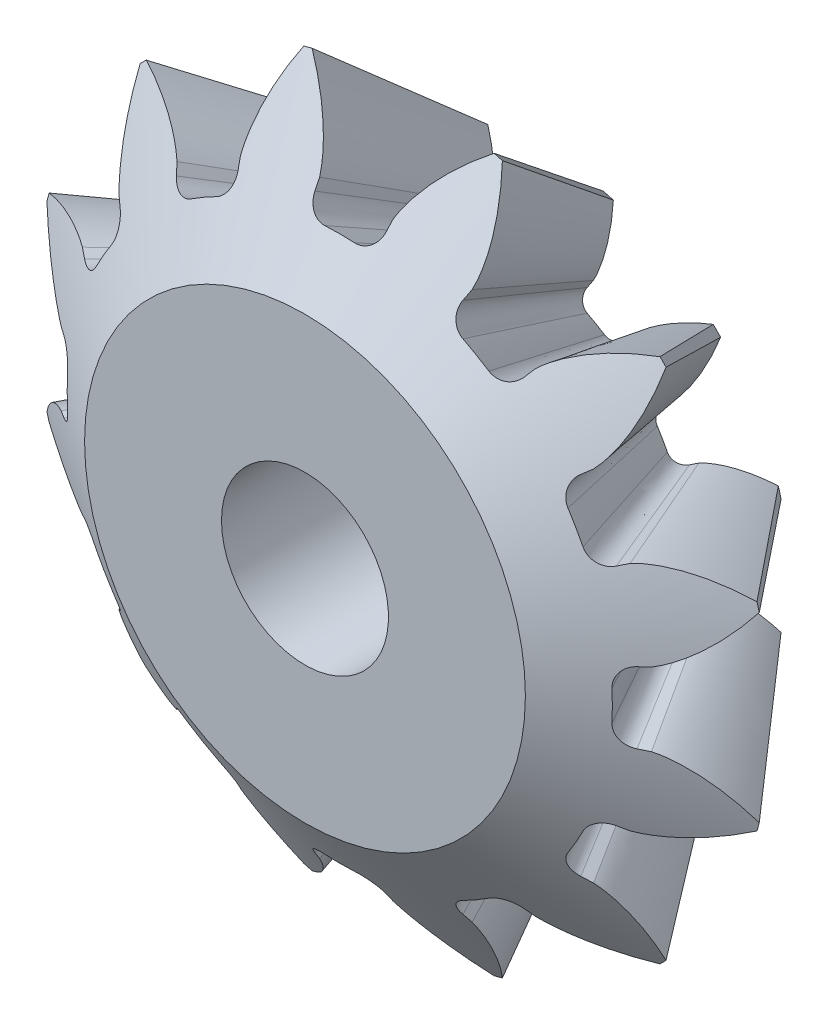
SolidWorks part; units mm, degrees
ref_plane "Front Plane" through (0, 0, 0) normal (0, 0, 1) x (1, 0, 0)
ref_plane "Top Plane" through (0, 0, 0) normal (0, 1, 0) x (1, 0, 0)
ref_plane "Right Plane" through (0, 0, 0) normal (1, 0, 0) x (0, 0, -1)
ref_axis "Gear Axis" through (0, 0, -1.3521) along (0, 0, 1)
sketch "Blank Sketch" plane through (0, 0, 0) normal (0, 1, 0) x (1, 0, 0)
  line L0 (0, 0) -> (0, -27.0416) construction
  line L1 (0, 0) -> (15, -22.5) construction
  line L2 (0, 0) -> (10.0077, -15.0115) construction
  line L3 (6.2136, -17.5409) -> (11.62, -13.9367)
  line L4 (11.62, -13.9367) -> (17.6117, -20.7589)
  line L5 (17.6117, -20.7589) -> (10.5604, -25.4597)
  line L6 (10.5604, -25.4597) -> (4, -25.4597)
  line L7 (4, -25.4597) -> (4, -17.5409)
  line L8 (4, -17.5409) -> (6.2136, -17.5409)
  line L9 (15, -22.5) -> (17.6117, -20.7589) construction
  line L10 (15, -22.5) -> (10.5604, -25.4597) construction
  line L11 (10.0077, -15.0115) -> (6.2136, -17.5409) construction
  dimension "Axis" = 27.0416
  dimension "Cone" = 33.69
  dimension "Heel" = 27.0416
  dimension "Toe Cone" = 33.69
  dimension "Toe" = 18.0416
  dimension "Heel Square" = 90
  dimension "Addendum" = 3.1389
  dimension "Root Square" = 90
  dimension "Heel Rim" = 5.3357
  dimension "Toe Square" = 90
  dimension "Toe Rim" = 4.5599
  dimension "Front Square" = 90
  dimension "Face" = 7.602
  dimension "Back" = 6.5604
  dimension "Front" = 2.2136
revolve "Blank" add sketch "Blank Sketch" angle 360 about L0
sketch "Cone Sketch" plane through (0, 0, 0) normal (0, 1, 0) x (1, 0, 0)
  line L0 (0, 0) -> (0, -27.0416) construction
  line L1 (0, 0) -> (16.3868, -24.5801)
  line L2 (0, 0) -> (8.6209, -12.9314)
  dimension "Axis" = 27.0416
  dimension "Toe Cone" = 33.69
  dimension "Heel Cone" = 33.69
  dimension "Heel" = 29.5416
  dimension "Toe" = 15.5416
ref_plane "Heel Plane" through (16.3868, 0, 24.5801) normal (0.5547, 0, 0.8321) x (0.8321, 0, -0.5547)
ref_plane "Toe Plane" through (8.6209, 0, 12.9314) normal (0.5547, 0, 0.8321) x (0.8321, 0, -0.5547)
sketch "Heel Section Sketch" plane through (16.3868, 0, 24.5801) normal (0.5547, 0, 0.8321) x (0.8321, 0, -0.5547)
  line L0 (0, 0) -> (-19.6944, 0) construction
  line L1 (-1.0889, 1.9222) -> (-1.6346, 1.8659)
  line L2 (-1.0889, -1.9222) -> (-1.6346, -1.8659)
  line L3 (4.9712, 7.7503) -> (4.9712, -7.7503)
  arc A0 (-1.6346, 1.8659) -> (-2.5646, 0.786) centre (-1.5279, 0.8335) ccw
  arc A1 (-2.5646, -0.786) -> (-1.6346, -1.8659) centre (-1.5279, -0.8335) ccw
  arc A2 (-2.5646, -0.786) -> (-2.5646, 0.786) centre (-19.6944, 0) ccw
  spline S0 degree 4 poles (-1.2507, 1.887) (-1.2032, 1.896) (-1.1208, 1.9133) (-1.0358, 1.9352) (-0.8462, 1.9918) (-0.6823, 2.0516) (-0.464, 2.1381) (-0.2472, 2.238) (-0.0046, 2.3596) (0.2268, 2.4884) (0.4574, 2.6259) (0.6814, 2.7703) (0.921, 2.9344) (1.2087, 3.1455) (1.5406, 3.4086) (1.9115, 3.7305) (2.2985, 4.0977) (2.6707, 4.4833) (3.0253, 4.8797) (3.3677, 5.2955) (3.6895, 5.7131) (4.0058, 6.1591) (4.2547, 6.5304) (4.4822, 6.8974) (4.6632, 7.1957) (4.8973, 7.6113) (5.0277, 7.8523) (5.2374, 8.2598) (5.307, 8.4069) (5.363, 8.5216) knots 0 0 0 0 0 0.016753 0.031571 0.050064 0.068907 0.096646 0.124386 0.152126 0.179865 0.207605 0.235344 0.263084 0.300343 0.355823 0.411302 0.466781 0.52226 0.577739 0.633218 0.688697 0.744176 0.799656 0.827395 0.855135 0.910614 0.955307 1 1 1 1 1 construction
  spline S1 degree 4 poles (-1.0889, 1.9222) (-1.058, 1.9301) (-0.9897, 1.9489) (-0.8462, 1.9918) (-0.6823, 2.0516) (-0.464, 2.1381) (-0.2472, 2.238) (-0.0046, 2.3596) (0.2268, 2.4884) (0.4574, 2.6259) (0.6814, 2.7703) (0.921, 2.9344) (1.2087, 3.1455) (1.5406, 3.4086) (1.9115, 3.7305) (2.2985, 4.0977) (2.6707, 4.4833) (3.0253, 4.8797) (3.3677, 5.2955) (3.6895, 5.7131) (4.0058, 6.1591) (4.2547, 6.5304) (4.4822, 6.8974) (4.6632, 7.1957) (4.83, 7.4919) (4.9147, 7.6452) (4.9712, 7.7503) knots 0.016753 0.016753 0.016753 0.016753 0.016753 0.031571 0.050064 0.068907 0.096646 0.124386 0.152126 0.179865 0.207605 0.235344 0.263084 0.300343 0.355823 0.411302 0.466781 0.52226 0.577739 0.633218 0.688697 0.744176 0.799656 0.827395 0.855135 0.910614 0.910614 0.910614 0.910614 0.910614
  spline S2 degree 4 poles (-1.2507, -1.887) (-1.2032, -1.896) (-1.1208, -1.9133) (-1.0358, -1.9352) (-0.8462, -1.9918) (-0.6823, -2.0516) (-0.464, -2.1381) (-0.2472, -2.238) (-0.0046, -2.3596) (0.2268, -2.4884) (0.4574, -2.6259) (0.6814, -2.7703) (0.921, -2.9344) (1.2087, -3.1455) (1.5406, -3.4086) (1.9115, -3.7305) (2.2985, -4.0977) (2.6707, -4.4833) (3.0253, -4.8797) (3.3677, -5.2955) (3.6895, -5.7131) (4.0058, -6.1591) (4.2547, -6.5304) (4.4822, -6.8974) (4.6632, -7.1957) (4.8973, -7.6113) (5.0277, -7.8523) (5.2374, -8.2598) (5.307, -8.4069) (5.363, -8.5216) knots 0 0 0 0 0 0.016753 0.031571 0.050064 0.068907 0.096646 0.124386 0.152126 0.179865 0.207605 0.235344 0.263084 0.300343 0.355823 0.411302 0.466781 0.52226 0.577739 0.633218 0.688697 0.744176 0.799656 0.827395 0.855135 0.910614 0.955307 1 1 1 1 1 construction
  spline S3 degree 4 poles (-1.0889, -1.9222) (-1.058, -1.9301) (-0.9897, -1.9489) (-0.8462, -1.9918) (-0.6823, -2.0516) (-0.464, -2.1381) (-0.2472, -2.238) (-0.0046, -2.3596) (0.2268, -2.4884) (0.4574, -2.6259) (0.6814, -2.7703) (0.921, -2.9344) (1.2087, -3.1455) (1.5406, -3.4086) (1.9115, -3.7305) (2.2985, -4.0977) (2.6707, -4.4833) (3.0253, -4.8797) (3.3677, -5.2955) (3.6895, -5.7131) (4.0058, -6.1591) (4.2547, -6.5304) (4.4822, -6.8974) (4.6632, -7.1957) (4.83, -7.4919) (4.9147, -7.6452) (4.9712, -7.7503) knots 0.016753 0.016753 0.016753 0.016753 0.016753 0.031571 0.050064 0.068907 0.096646 0.124386 0.152126 0.179865 0.207605 0.235344 0.263084 0.300343 0.355823 0.411302 0.466781 0.52226 0.577739 0.633218 0.688697 0.744176 0.799656 0.827395 0.855135 0.910614 0.910614 0.910614 0.910614 0.910614
  dimension "Root" = 17.1478
  dimension "Fillet" = 1.0378
  dimension "Centre" = 19.6944
sketch "Toe Section Sketch" plane through (8.6209, 0, 12.9314) normal (0.5547, 0, 0.8321) x (0.8321, 0, -0.5547)
  line L0 (0, 0) -> (-10.3611, 0) construction
  line L1 (-0.5729, 1.0113) -> (-0.8599, 0.9816)
  line L2 (-0.5729, -1.0113) -> (-0.8599, -0.9816)
  line L3 (2.6153, 4.0774) -> (2.6153, -4.0774)
  arc A0 (-0.8599, 0.9816) -> (-1.3492, 0.4135) centre (-0.8038, 0.4385) ccw
  arc A1 (-1.3492, -0.4135) -> (-0.8599, -0.9816) centre (-0.8038, -0.4385) ccw
  arc A2 (-1.3492, -0.4135) -> (-1.3492, 0.4135) centre (-10.3611, 0) ccw
  spline S0 degree 4 poles (-0.658, 0.9927) (-0.633, 0.9975) (-0.5896, 1.0066) (-0.5449, 1.0181) (-0.4452, 1.0479) (-0.3589, 1.0793) (-0.2441, 1.1248) (-0.13, 1.1774) (-0.0024, 1.2414) (0.1193, 1.3091) (0.2407, 1.3815) (0.3584, 1.4574) (0.4846, 1.5439) (0.6358, 1.6546) (0.8107, 1.7936) (1.0052, 1.9619) (1.2098, 2.1568) (1.4042, 2.357) (1.593, 2.5698) (1.7694, 2.7815) (1.9449, 3.0128) (2.1009, 3.2281) (2.2685, 3.4846) (2.3965, 3.6866) (2.5615, 3.9767) (2.6479, 4.1363) (2.7514, 4.3381) (2.7948, 4.4281) (2.8204, 4.4812) knots 0 0 0 0 0 0.016753 0.031571 0.050064 0.068907 0.096646 0.124386 0.152126 0.179865 0.207605 0.235344 0.263084 0.300343 0.355823 0.411302 0.466781 0.52226 0.577739 0.633218 0.688697 0.744176 0.799656 0.855135 0.910614 0.955307 1 1 1 1 1 construction
  spline S1 degree 4 poles (-0.5729, 1.0113) (-0.5566, 1.0154) (-0.5207, 1.0253) (-0.4452, 1.0479) (-0.3589, 1.0793) (-0.2441, 1.1248) (-0.13, 1.1774) (-0.0024, 1.2414) (0.1193, 1.3091) (0.2407, 1.3815) (0.3584, 1.4574) (0.4846, 1.5439) (0.6358, 1.6546) (0.8107, 1.7936) (1.0052, 1.9619) (1.2098, 2.1568) (1.4042, 2.357) (1.593, 2.5698) (1.7694, 2.7815) (1.9449, 3.0128) (2.1009, 3.2281) (2.2685, 3.4846) (2.3965, 3.6866) (2.5266, 3.9153) (2.5856, 4.0221) (2.6153, 4.0774) knots 0.016753 0.016753 0.016753 0.016753 0.016753 0.031571 0.050064 0.068907 0.096646 0.124386 0.152126 0.179865 0.207605 0.235344 0.263084 0.300343 0.355823 0.411302 0.466781 0.52226 0.577739 0.633218 0.688697 0.744176 0.799656 0.855135 0.910614 0.910614 0.910614 0.910614 0.910614
  spline S2 degree 4 poles (-0.658, -0.9927) (-0.633, -0.9975) (-0.5896, -1.0066) (-0.5449, -1.0181) (-0.4452, -1.0479) (-0.3589, -1.0793) (-0.2441, -1.1248) (-0.13, -1.1774) (-0.0024, -1.2414) (0.1193, -1.3091) (0.2407, -1.3815) (0.3584, -1.4574) (0.4846, -1.5439) (0.6358, -1.6546) (0.8107, -1.7936) (1.0052, -1.9619) (1.2098, -2.1568) (1.4042, -2.357) (1.593, -2.5698) (1.7694, -2.7815) (1.9449, -3.0128) (2.1009, -3.2281) (2.2685, -3.4846) (2.3965, -3.6866) (2.5615, -3.9767) (2.6479, -4.1363) (2.7514, -4.3381) (2.7948, -4.4281) (2.8204, -4.4812) knots 0 0 0 0 0 0.016753 0.031571 0.050064 0.068907 0.096646 0.124386 0.152126 0.179865 0.207605 0.235344 0.263084 0.300343 0.355823 0.411302 0.466781 0.52226 0.577739 0.633218 0.688697 0.744176 0.799656 0.855135 0.910614 0.955307 1 1 1 1 1 construction
  spline S3 degree 4 poles (-0.5729, -1.0113) (-0.5566, -1.0154) (-0.5207, -1.0253) (-0.4452, -1.0479) (-0.3589, -1.0793) (-0.2441, -1.1248) (-0.13, -1.1774) (-0.0024, -1.2414) (0.1193, -1.3091) (0.2407, -1.3815) (0.3584, -1.4574) (0.4846, -1.5439) (0.6358, -1.6546) (0.8107, -1.7936) (1.0052, -1.9619) (1.2098, -2.1568) (1.4042, -2.357) (1.593, -2.5698) (1.7694, -2.7815) (1.9449, -3.0128) (2.1009, -3.2281) (2.2685, -3.4846) (2.3965, -3.6866) (2.5266, -3.9153) (2.5856, -4.0221) (2.6153, -4.0774) knots 0.016753 0.016753 0.016753 0.016753 0.016753 0.031571 0.050064 0.068907 0.096646 0.124386 0.152126 0.179865 0.207605 0.235344 0.263084 0.300343 0.355823 0.411302 0.466781 0.52226 0.577739 0.633218 0.688697 0.744176 0.799656 0.855135 0.910614 0.910614 0.910614 0.910614 0.910614
  dimension "Root" = 9.0213
  dimension "Fillet" = 0.546
  dimension "Centre" = 10.3611
loft "Tooth Space" cut profiles "Heel Section Sketch", "Toe Section Sketch"
pattern_circular "Teeth" count 12 over 360 about axis through (0, 0, -1.3521) along (0, 0, 1) of "Tooth Space"
equation "\"No. of Teeth\"= 12"
equation "\"Module\"= 2.5"
equation "\"Bore Diameter\"= 8"
equation "\"Pressure Angle\"= 20"
equation "\"Shaft Angle\"= 90"
equation "\"Mate Teeth\"= 18"
equation "\"Pitch Cone Angle\"= IIF ( ( \"Mate Teeth\" / \"No. of Teeth\" + cos ( \"Shaft Angle\" ) ) > 0 , atn ( sin ( \"Shaft Angle\" ) / ( \"Mate Teeth\" / \"No. of Teeth\" + cos ( \"Shaft Angle\" ) ) ) , 180 + atn ( sin ( \"Shaft Angle\" ) / ( \"Mate Teeth\" / \"No. of Teeth\" + cos ( \"Shaft Angle\" ) ) ) )"
equation "\"Mate Cone Angle\"= \"Shaft Angle\" - \"Pitch Cone Angle\""
equation "\"Addendum\"= IIF ( \"No. of Teeth\" >= \"Mate Teeth\" , 0.54 * \"Module\" + 0.46 * \"Module\" / ( ( \"No. of Teeth\" * cos ( \"Mate Cone Angle\" ) ) / ( \"Mate Teeth\" * cos ( \"Pitch Cone Angle\" ) ) ) , 2 * \"Module\" - ( 0.54 * \"Module\" + 0.46 * \"Module\" / ( ( \"Mate Teeth\" * cos ( \"Pitch Cone Angle\" ) ) / ( \"No. of Teeth\" * cos ( \"Mate Cone Angle\" ) ) ) ) )"
equation "\"Outer Diameter\"= \"No. of Teeth\" * \"Module\" + 2 * \"Addendum\" * cos ( \"Pitch Cone Angle\" )"
equation "\"Pitch Diameter\"= \"No. of Teeth\" * \"Module\""
equation "\"Backlash\"= 0.3 * \"Module\""
equation "\"Arc Length\"= ( ( \"Module\" * pi ) / 2 + \"Backlash\" - 2 * ( \"Addendum\" - \"Module\" ) * tan ( \"Pressure Angle\" ) )"
equation "\"Fillet Radius\"= 0.38 * \"Module\""
equation "\"Mate Addendum\"= 2 * \"Module\" - \"Addendum\""
equation "\"Dedendum\"= 2.188 * \"Module\" - \"Addendum\""
equation "\"Tooth Depth\"= \"Addendum\" + \"Dedendum\""
equation "\"Mate Dedendum\"= 2.188 * \"Module\" - \"Mate Addendum\""
equation "\"Face Width\"= 9"
equation "\"Cone Distance\"= \"Pitch Diameter\" / ( 2 * sin ( \"Pitch Cone Angle\" ) )"
equation "\"Dedendum Angle\"= atn ( \"Dedendum\" / \"Cone Distance\" )"
equation "\"Mate Dedendum Angle\"= atn ( \"Mate Dedendum\" / \"Cone Distance\" )"
equation "\"Face Angle\"= \"Pitch Cone Angle\" + \"Mate Dedendum Angle\""
equation "\"Root Angle\"= \"Pitch Cone Angle\" - \"Dedendum Angle\""
equation "\"Overrun\"= \"Module\""
equation "\"Back Cone Pitch Diameter\"= \"Pitch Diameter\" / cos ( \"Pitch Cone Angle\" )"
equation "\"Back Cone Outer Diameter\"= \"Back Cone Pitch Diameter\" + 2 * \"Addendum\""
equation "\"Root Diameter\"= \"Back Cone Outer Diameter\" - 2 * \"Tooth Depth\""
equation "\"Base Diameter\"= \"Back Cone Pitch Diameter\" * cos ( \"Pressure Angle\" )"
equation "\"Base Radius\"= \"Base Diameter\" / 2"
equation "\"Tooth Thickness\"= \"Module\" * pi - \"Arc Length\""
equation "\"Half Space Angle\"= ( \"Arc Length\" / \"Back Cone Pitch Diameter\" ) * 180 / pi"
equation "\"Involute Fn\"= tan ( \"Pressure Angle\" ) - \"Pressure Angle\" * pi / 180"
equation "\"Flank Offset\"= \"Arc Length\" / \"Back Cone Pitch Diameter\" - \"Involute Fn\""
equation "\"Tip Cap Diameter\"= \"Back Cone Outer Diameter\" + 2 * \"Module\""
equation "\"Flank Start Diameter\"= IIF ( \"Base Diameter\" >= ( \"Root Diameter\" + 3 * \"Fillet Radius\" ) , \"Base Diameter\" , \"Root Diameter\" + 3 * \"Fillet Radius\" )"
equation "\"Involute t1\"= ( abs ( ( \"Flank Start Diameter\" / \"Base Diameter\" ) ^ 2 - 1 ) ) ^ 0.5"
equation "\"Involute t2\"= ( abs ( ( \"Tip Cap Diameter\" / \"Base Diameter\" ) ^ 2 - 1 ) ) ^ 0.5"
equation "\"Flank Arc Radius\"= ( \"Back Cone Pitch Diameter\" / 2 ) * sin ( \"Pressure Angle\" )"
equation "\"Flank Centre Angle\"= \"Half Space Angle\" + \"Pressure Angle\""
equation "\"Heel Distance\"= \"Cone Distance\" + \"Overrun\""
equation "\"Toe Distance\"= \"Cone Distance\" - \"Face Width\" - \"Overrun\""
equation "\"Heel Scale\"= \"Heel Distance\" / \"Cone Distance\""
equation "\"Toe Scale\"= \"Toe Distance\" / \"Cone Distance\""
equation "\"Heel Virtual Radius\"= \"Heel Distance\" * tan ( \"Pitch Cone Angle\" )"
equation "\"Toe Virtual Radius\"= \"Toe Distance\" * tan ( \"Pitch Cone Angle\" )"
equation "\"Axis@Blank Sketch\"= \"Cone Distance\""
equation "\"Cone@Blank Sketch\"= \"Pitch Cone Angle\""
equation "\"Heel@Blank Sketch\"= \"Cone Distance\""
equation "\"Toe Cone@Blank Sketch\"= \"Pitch Cone Angle\""
equation "\"Toe@Blank Sketch\"= \"Cone Distance\" - \"Face Width\""
equation "\"Addendum@Blank Sketch\"= \"Addendum\""
equation "\"Heel Rim@Blank Sketch\"= \"Dedendum\" + \"Module\" / cos ( \"Pitch Cone Angle\" )"
equation "\"Toe Rim@Blank Sketch\"= \"Dedendum\" - \"Face Width\" * tan ( \"Dedendum Angle\" ) + \"Module\" / cos ( \"Pitch Cone Angle\" )"
equation "\"Face@Blank Sketch\"= \"Mate Dedendum Angle\""
equation "\"Back@Blank Sketch\"= \"Cone Distance\" * sin ( \"Pitch Cone Angle\" ) - \"Dedendum\" * cos ( \"Pitch Cone Angle\" ) - \"Module\" - \"Bore Diameter\" / 2"
equation "\"Front@Blank Sketch\"= ( \"Cone Distance\" - \"Face Width\" ) * sin ( \"Pitch Cone Angle\" ) - ( \"Dedendum\" - \"Face Width\" * tan ( \"Dedendum Angle\" ) + \"Module\" / cos ( \"Pitch Cone Angle\" ) ) * cos ( \"Pitch Cone Angle\" ) - \"Bore Diameter\" / 2"
equation "\"Axis@Cone Sketch\"= \"Cone Distance\""
equation "\"Heel Cone@Cone Sketch\"= \"Pitch Cone Angle\""
equation "\"Heel@Cone Sketch\"= \"Heel Distance\""
equation "\"Toe Cone@Cone Sketch\"= \"Pitch Cone Angle\""
equation "\"Toe@Cone Sketch\"= \"Toe Distance\""
equation "\"Centre@Heel Section Sketch\"= \"Heel Virtual Radius\""
equation "\"Root@Heel Section Sketch\"= ( \"Root Diameter\" / 2 ) * \"Heel Scale\""
equation "\"Fillet@Heel Section Sketch\"= ( \"Fillet Radius\" ) * \"Heel Scale\""
equation "\"Centre@Toe Section Sketch\"= \"Toe Virtual Radius\""
equation "\"Root@Toe Section Sketch\"= ( \"Root Diameter\" / 2 ) * \"Toe Scale\""
equation "\"Fillet@Toe Section Sketch\"= ( \"Fillet Radius\" ) * \"Toe Scale\""
equation "\"Count@Teeth\"= \"No. of Teeth\""
